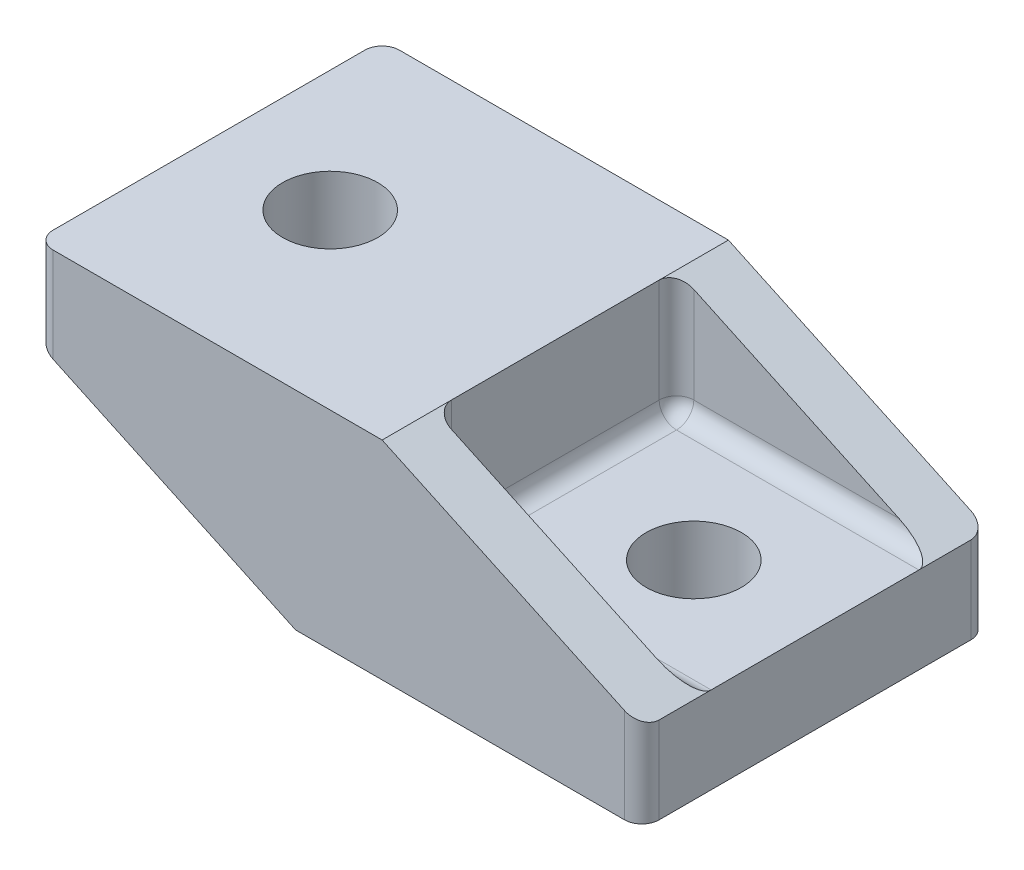
SolidWorks part; units mm, degrees
ref_plane "Front Plane" through (0, 0, 0) normal (0, 0, 1) x (1, 0, 0)
ref_plane "Top Plane" through (0, 0, 0) normal (0, 1, 0) x (1, 0, 0)
ref_plane "Right Plane" through (0, 0, 0) normal (1, 0, 0) x (0, 0, -1)
sketch "Sketch1" plane through (0, 0, 0) normal (0, 0, 1) x (1, 0, 0)
  line L0 (0, 0) -> (0, 7)
  line L1 (0, 7) -> (-15, 7)
  line L2 (-15, 7) -> (-15, 12)
  line L3 (-15, 12) -> (5, 12)
  line L4 (5, 12) -> (5, 5)
  line L5 (5, 5) -> (20, 5)
  line L6 (20, 5) -> (20, 0)
  line L7 (20, 0) -> (0, 0)
  dimension "D1" = 5
  dimension "D2" = 5
  dimension "D3" = 20
  dimension "D4" = 5
  dimension "D5" = 15
  dimension "D6" = 12
extrude "Boss-Extrude1" add sketch "Sketch1" along normal mid plane 20
sketch "Sketch2" plane through (0, 12, 0) normal (0, 1, 0) x (1, 0, 0)
  line L0 (-15, -10) -> (-15, 10) construction
  circle A0 centre (-8, 0) radius 2.75
  dimension "D1" = 5.5
  dimension "D2" = 7
extrude "Cut-Extrude1" cut sketch "Sketch2" against normal through all
sketch "Sketch3" plane through (0, 5, 0) normal (0, 1, 0) x (1, 0, 0)
  line L0 (20, -10) -> (20, 10) construction
  circle A0 centre (13, 0) radius 2.75
  dimension "D1" = 5.5
  dimension "D2" = 7
extrude "Cut-Extrude2" cut sketch "Sketch3" against normal through all
sketch "Sketch5" plane through (0, 0, -10) normal (0, 0, -1) x (-1, 0, 0)
  line L0 (-20, 5) -> (-5, 12)
rib "Rib7" sketch "Sketch5" sketch "Sketch5" thickness 3 extrusion direction parallel to sketch draft on no parameters "D1"=3
sketch "Sketch6" plane through (0, 0, -10) normal (0, 0, -1) x (-1, 0, 0)
  line L0 (15, 7) -> (0, 0)
  line L2 (0, 7) -> (0, 0) construction
rib "Rib8" sketch "Sketch6" sketch "Sketch6" thickness 3 extrusion direction parallel to sketch draft on no parameters "D1"=3
mirror "Mirror1" about plane through (0, 0, 0) normal (0, 0, 1) of "Rib8", "Rib7"
fillet "Fillet1" radius 1 10 edges at (5, 8.5, -7) (12.5, 5, -7) (12.5, 5, 7) (5, 8.5, 7) (5, 5, 0) (0, 7, 0) (0, 3.5, -7) (0, 3.5, 7) (-7.5, 7, 7) (-7.5, 7, -7)
fillet "Fillet2" radius 1 4 edges at (20, 2.5, -10) (20, 2.5, 10) (-15, 9.5, 10) (-15, 9.5, -10)
